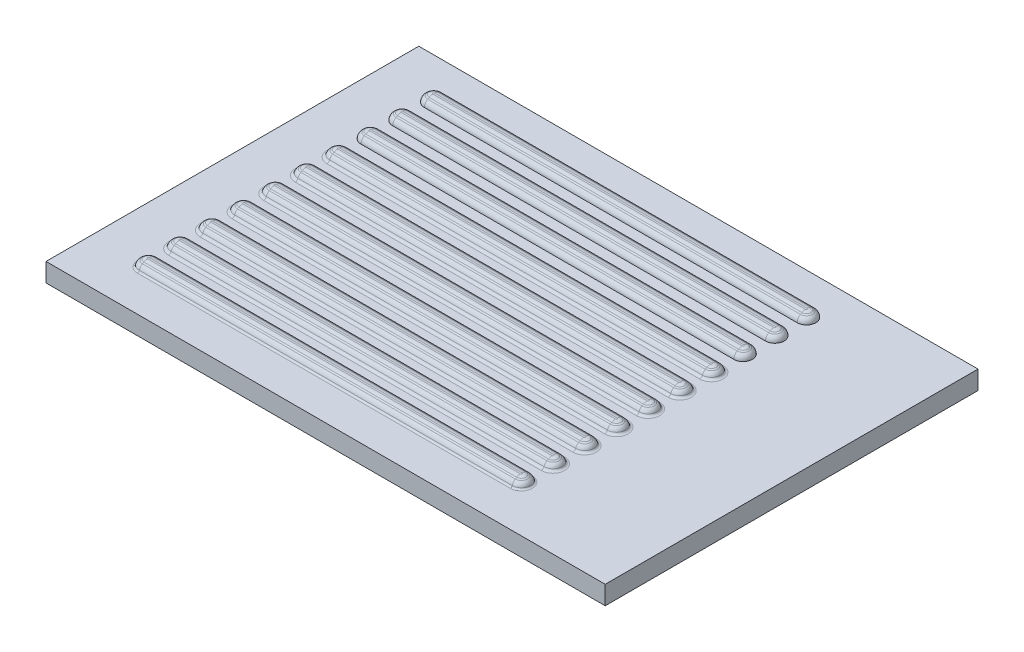
SolidWorks part; units mm, degrees
ref_plane "Front Plane" through (0, 0, 0) normal (0, 0, 1) x (1, 0, 0)
ref_plane "Top Plane" through (0, 0, 0) normal (0, 1, 0) x (1, 0, 0)
ref_plane "Right Plane" through (0, 0, 0) normal (1, 0, 0) x (0, 0, -1)
sketch "Sketch1" plane through (0, 0, 0) normal (0, 1, 0) x (1, 0, 0)
  line L1 (-15000, 10000) -> (15000, 10000)
  line L2 (-15000, 10000) -> (-15000, -10000)
  line L3 (-15000, -10000) -> (15000, -10000)
  line L4 (15000, 10000) -> (15000, -10000)
  line L5 (-15000, 10000) -> (15000, -10000) construction
  line L6 (-15000, -10000) -> (15000, 10000) construction
  point P0 (0, 0)
  dimension "D1" = 20000
  dimension "D2" = 30000
extrude "Boss-Extrude1" add sketch "Sketch1" against normal blind 1000
sketch "Sketch3" plane through (0, 0, 0) normal (0, 1, 0) x (1, 0, 0)
  line L0 (-12000, -7500) -> (8000, -7500) construction
  line L1 (-12000, -7000) -> (8000, -7000)
  line L2 (-12000, -8000) -> (8000, -8000)
  line L3 (-15000, -10000) -> (15000, -10000) construction
  line L4 (-15000, 10000) -> (-15000, -10000) construction
  arc A0 (-12000, -7000) -> (-12000, -8000) centre (-12000, -7500) ccw
  arc A1 (8000, -8000) -> (8000, -7000) centre (8000, -7500) ccw
  point P2 (-2000, -7500)
  dimension "D4" = 3000
  dimension "D1" = 1000
  dimension "D2" = 20000
  dimension "D3" = 2500
extrude "Boss-Extrude2" add sketch "Sketch3" along normal blind 400
chamfer "Chamfer1" distance 200 angle 60 4 edges at (-2000, 400, 7000) (8500, 400, 7500) (-2000, 400, 8000) (-12500, 400, 7500) first distance on face at (-2000, 200, 7000) first distance on face at (8250, 200, 7500) first distance on face at (-2000, 200, 8000) first distance on face at (-12250, 200, 7500)
fillet "Fillet3" radius 400 4 edges at (-2000, 400, 7653.5898) (-12153.5898, 400, 7500) (-2000, 400, 7346.4102) (8153.5898, 400, 7500)
fillet "Fillet4" radius 350 4 edges at (-12500, 200, 7500) (-2000, 200, 8000) (8500, 200, 7500) (-2000, 200, 7000)
fillet "Fillet2" radius 100 4 edges at (8500, 0, 7500) (-2000, 0, 7000) (-12500, 0, 7500) (-2000, 0, 8000)
pattern_linear "LPattern3" count 10 spacing 1700 along (0, 0, -1) of "Boss-Extrude2", "Chamfer1", "Fillet3", "Fillet4"
fillet "Fillet5" radius 150 4 edges at (-2000, 0, 6300) (-12500, 0, 5800) (-2000, 0, 5300) (8500, 0, 5800)
fillet "Fillet6" radius 150 4 edges at (-2000, 0, 4600) (-12500, 0, 4100) (-2000, 0, 3600) (8500, 0, 4100)
fillet "Fillet7" radius 150 4 edges at (-2000, 0, 2900) (-12500, 0, 2400) (-2000, 0, 1900) (8500, 0, 2400)
fillet "Fillet8" radius 150 4 edges at (-2000, 0, 1200) (-12500, 0, 700) (-2000, 0, 200) (8500, 0, 700)
fillet "Fillet9" radius 150 4 edges at (8500, 0, -1000) (-2000, 0, -500) (-12500, 0, -1000) (-2000, 0, -1500)
fillet "Fillet10" radius 150 4 edges at (-2000, 0, -2200) (-12500, 0, -2700) (-2000, 0, -3200) (8500, 0, -2700)
